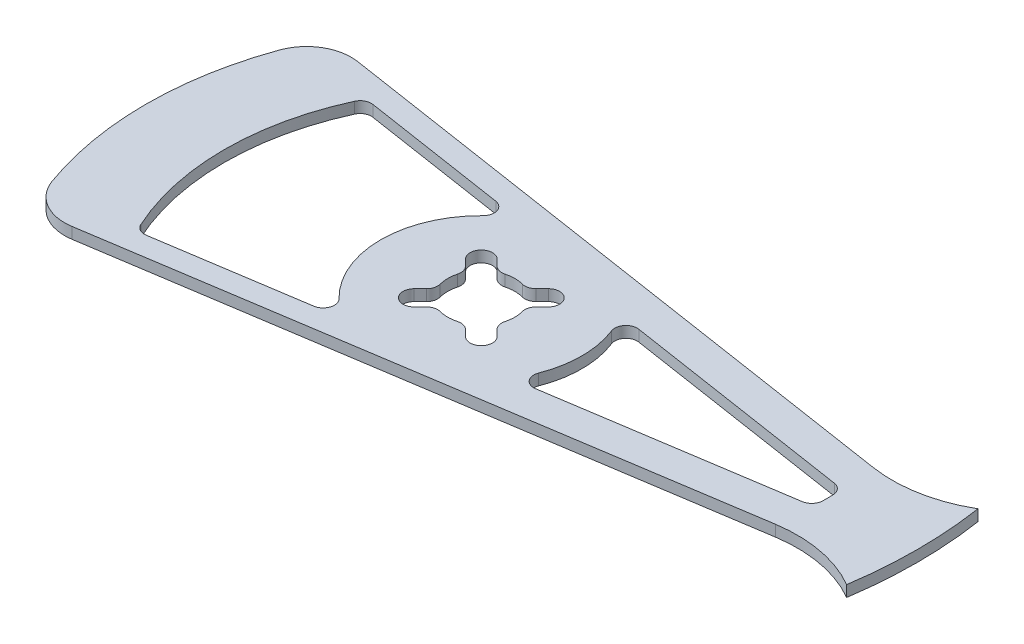
SolidWorks part; units mm, degrees
material "AISI 4340 Steel, normalized"
ref_plane "Front Plane" through (0, 0, 0) normal (0, 0, 1) x (1, 0, 0)
ref_plane "Top Plane" through (0, 0, 0) normal (0, 1, 0) x (1, 0, 0)
ref_plane "Right Plane" through (0, 0, 0) normal (1, 0, 0) x (0, 0, -1)
other "Center of Mass"
sketch "Sketch1" plane through (0, 0, 0) normal (0, 1, 0) x (1, 0, 0)
  line L0 (-170.9166, 84.1295) -> (194.8729, 27.8292)
  line L1 (-170.9166, -84.1295) -> (194.8729, -27.8292)
  line L2 (-130.6087, 65.076) -> (-28.7411, 49.3971)
  line L3 (-130.6087, -65.076) -> (-28.7411, -49.3971)
  line L4 (47.8972, 31.1766) -> (196.6759, 8.2773)
  line L5 (47.8972, -31.1766) -> (196.6759, -8.2773)
  line L6 (-23.5401, 14.5599) -> (-17.1901, 8.2099)
  line L7 (-19.05, -19.05) -> (19.05, -19.05) construction
  line L8 (-19.05, -19.05) -> (-19.05, 19.05) construction
  line L9 (-19.05, 19.05) -> (19.05, 19.05) construction
  line L10 (19.05, -19.05) -> (19.05, 19.05) construction
  line L11 (-19.05, -19.05) -> (19.05, 19.05) construction
  line L12 (-19.05, 19.05) -> (19.05, -19.05) construction
  line L13 (-14.5599, 23.5401) -> (-8.2099, 17.1901)
  line L14 (23.5401, 14.5599) -> (17.1901, 8.2099)
  line L15 (14.5599, 23.5401) -> (8.2099, 17.1901)
  line L16 (14.5599, -23.5401) -> (8.2099, -17.1901)
  line L17 (23.5401, -14.5599) -> (17.1901, -8.2099)
  line L18 (-23.5401, -14.5599) -> (-17.1901, -8.2099)
  line L19 (-14.5599, -23.5401) -> (-8.2099, -17.1901)
  line L20 (0, 0) -> (244.8246, 37.3019) construction
  circle A0 centre (0, 0) radius 57.15 construction
  circle A1 centre (0, 0) radius 247.65 construction
  arc A2 (244.8246, 37.3019) -> (244.8246, -37.3019) centre (0, 0) cw
  arc A3 (194.8729, -27.8292) -> (244.8246, -37.3019) centre (206.4647, -103.1423) cw
  arc A4 (194.8729, 27.8292) -> (244.8246, 37.3019) centre (206.4647, 103.1423) ccw
  circle A5 centre (0, 0) radius 190.5 construction
  arc A6 (-170.9166, 84.1295) -> (-170.9166, -84.1295) centre (0, 0) ccw
  circle A7 centre (0, 0) radius 196.85 construction
  circle A8 centre (0, 0) radius 145.923 construction
  arc A9 (-130.6087, 65.076) -> (-130.6087, -65.076) centre (0, 0) ccw
  arc A10 (-28.7411, 49.3971) -> (-28.7411, -49.3971) centre (0, 0) ccw
  arc A11 (47.8972, 31.1766) -> (47.8972, -31.1766) centre (0, 0) cw
  arc A12 (196.6759, 8.2773) -> (196.6759, -8.2773) centre (0, 0) cw
  circle A13 centre (0, 0) radius 19.05
  circle A14 centre (-19.05, 19.05) radius 6.35
  circle A15 centre (19.05, 19.05) radius 6.35
  circle A16 centre (19.05, -19.05) radius 6.35
  circle A17 centre (-19.05, -19.05) radius 6.35
  point P18 (-190.5, 0)
  point P59 (0, 0)
  dimension "D1" = 495.3
  dimension "D2" = 50.8
  dimension "D3" = 17.5
  dimension "D4" = 114.3
  dimension "D5" = 57.15
  dimension "D6" = 76.2
  dimension "D9" = 44.577
  dimension "D12" = 38.1
  dimension "D14" = 12.7
  dimension "D15" = 4
  dimension "D7" = 12.7
  dimension "D8" = 12.7
  dimension "D10" = 19.05
  dimension "D11" = 19.05
  dimension "D13" = 38.1
extrude "Boss-Extrude1" add sketch "Sketch1" along normal blind 6.35 contours L0 A6 L1 A3 A2 A4 L2 A10 L3 A9 region at (11.2642, 0, -51.3405)
fillet "Fillet1" radius 6.35 8 edges at (47.8972, 3.175, 31.1766) (47.8972, 3.175, -31.1766) (196.6759, 3.175, -8.2773) (196.6759, 3.175, 8.2773) (-130.6087, 3.175, -65.076) (-130.6087, 3.175, 65.076) (-28.7411, 3.175, -49.3971) (-28.7411, 3.175, 49.3971)
fillet "Fillet2" radius 25.4 2 edges at (-170.9166, 3.175, -84.1295) (-170.9166, 3.175, 84.1295)
fillet "Fillet3" radius 6.35 8 edges at (-8.2099, 3.175, 17.1901) (8.2099, 3.175, 17.1901) (17.1901, 3.175, 8.2099) (17.1901, 3.175, -8.2099) (-8.2099, 3.175, -17.1901) (8.2099, 3.175, -17.1901) (-17.1901, 3.175, -8.2099) (-17.1901, 3.175, 8.2099)
